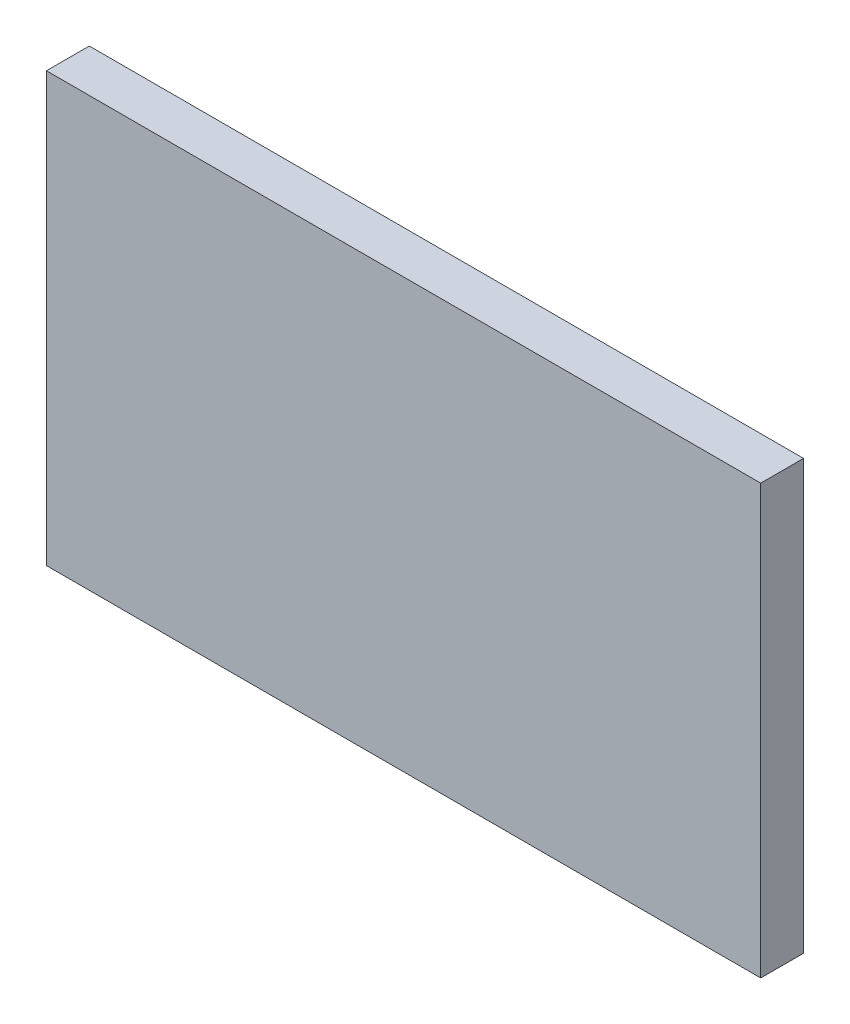
SolidWorks part; units mm, degrees
ref_plane "Ön Düzlem" through (0, 0, 0) normal (0, 0, 1) x (1, 0, 0)
ref_plane "Üst Düzlem" through (0, 0, 0) normal (0, 1, 0) x (1, 0, 0)
ref_plane "Sağ Düzlem" through (0, 0, 0) normal (1, 0, 0) x (0, 0, -1)
sketch "Çizim1" plane through (0, 0, 0) normal (0, 0, 1) x (1, 0, 0)
  line L1 (0, 0) -> (250, 0)
  line L2 (0, 0) -> (0, -150)
  line L3 (0, -150) -> (250, -150)
  line L4 (250, 0) -> (250, -150)
  dimension "D1" = 250
  dimension "D2" = 150
base flange "Taban-Flanş1" sketch "Çizim1" thickness 15 reverse thickness direction no parameters "D1"=8
sketch "Büküm-Çizgileri1" [suppressed] plane through (0, 0, 0) normal (0, 1, 0) x (1, 0, 0)
sketch "Sınırlandırma-Kutusu1" [suppressed] plane through (0, 0, 0) normal (0, 1, 0) x (1, 0, 0)
sheet metal parameters "Sac-Levha1" thickness 15 parameters "D1"=8
flat pattern "Düz-Çoğaltma1" [suppressed]
sketch "Büküm-Çizgileri2" plane through (0, 0, 0) normal (0, 1, 0) x (1, 0, 0)
sketch3d "Sınırlandırma-Kutusu2" [suppressed]
  line L0 (0, -150, 0) -> (250, -150, 0) construction
  line L1 (0, 0, 0) -> (250, 0, 0) construction
  line L2 (0, -150, 0) -> (0, 0, 0) construction
  line L3 (250, -150, 0) -> (250, 0, 0) construction
